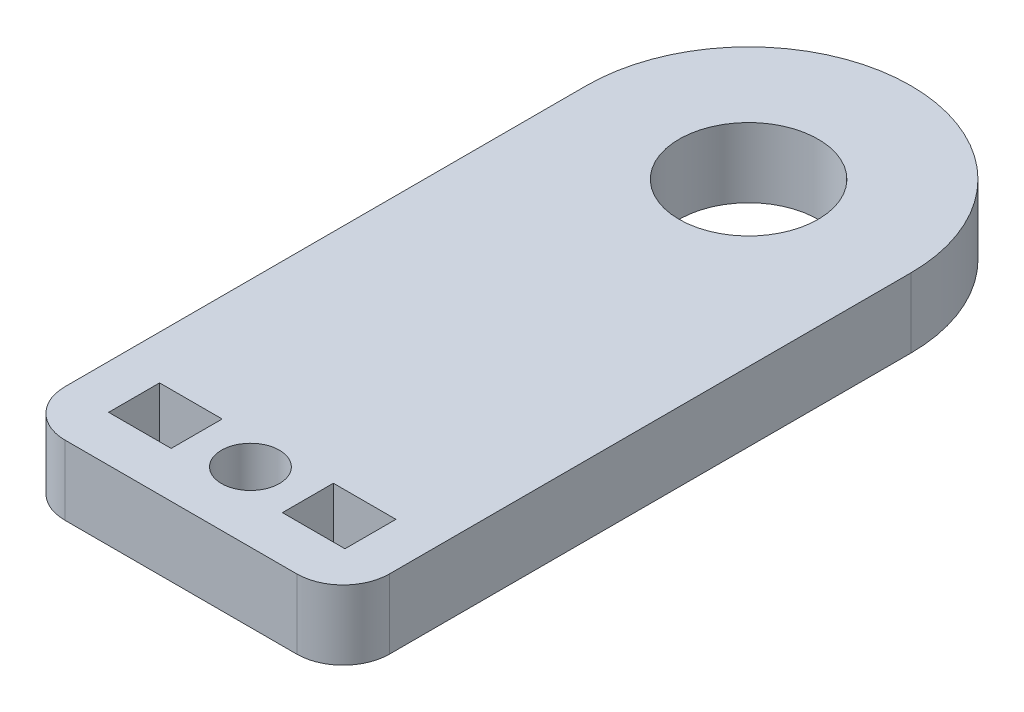
SolidWorks part; units mm, degrees
ref_plane "前视基准面" through (0, 0, 0) normal (0, 0, 1) x (1, 0, 0)
ref_plane "上视基准面" through (0, 0, 0) normal (0, 1, 0) x (1, 0, 0)
ref_plane "右视基准面" through (0, 0, 0) normal (1, 0, 0) x (0, 0, -1)
sketch "草图1" plane through (0, 0, 0) normal (0, 1, 0) x (1, 0, 0)
  line L0 (0, 12.25) -> (0, 2.25)
  line L1 (-7, -12.25) -> (7, -12.25)
  line L2 (-7, -12.25) -> (-7, 12.25)
  line L3 (-7, 12.25) -> (7, 12.25)
  line L4 (7, -12.25) -> (7, 12.25)
  line L5 (-7, -12.25) -> (7, 12.25) construction
  line L6 (-7, 12.25) -> (7, -12.25) construction
  line L7 (0, 0) -> (0, -12.25) construction
  line L8 (-2.4, -8.0707) -> (-5.1, -8.0707)
  line L9 (-2.4, -8.0707) -> (-2.4, -10.2707)
  line L10 (-2.4, -10.2707) -> (-5.1, -10.2707)
  line L11 (-5.1, -8.0707) -> (-5.1, -10.2707)
  line L12 (-2.4, -8.0707) -> (-5.1, -10.2707) construction
  line L13 (-2.4, -10.2707) -> (-5.1, -8.0707) construction
  line L14 (2.4, -10.2707) -> (5.1, -8.0707) construction
  line L15 (2.4, -8.0707) -> (5.1, -10.2707) construction
  line L16 (5.1, -8.0707) -> (5.1, -10.2707)
  line L17 (2.4, -10.2707) -> (5.1, -10.2707)
  line L18 (2.4, -8.0707) -> (2.4, -10.2707)
  line L19 (2.4, -8.0707) -> (5.1, -8.0707)
  circle A0 centre (0, 12.25) radius 7
  circle A1 centre (0, 12.25) radius 3
  circle A3 centre (0, -9.25) radius 1.25
  point P0 (0, 0)
  point P13 (-3.75, -9.1707)
  point P24 (3.75, -9.1707)
  dimension "D1" = 14
  dimension "D3" = 6
  dimension "D6" = 2.5
  dimension "D2" = 24.5
  dimension "D4" = 10
  dimension "D7" = 3
  dimension "D8" = 2.7
  dimension "D9" = 2.2
  dimension "D10" = 3.75
  dimension "D11" = 7
extrude "凸台-拉伸2" add sketch "草图1" along normal blind 3 contours A1 L3 A0 | A1 L3 A0 L0 | A1 L0 A0 L3 region at (3.3529, 0, -8.8971) region at (-3.3529, 0, -8.8971) region at (0, 0, -15.6029)
extrude "凸台-拉伸3" add sketch "草图1<4>" along normal blind 3 contours A0 L2 L1 L4 A3 region at (0, 0, 2.2462)
sketch "草图1<4>" plane through (0, 0, 0) normal (0, 1, 0) x (1, 0, 0) same geometry as "草图1"
fillet "圆角2" radius 2 2 edges at (7, 1.5, 12.25) (-7, 1.5, 12.25)
